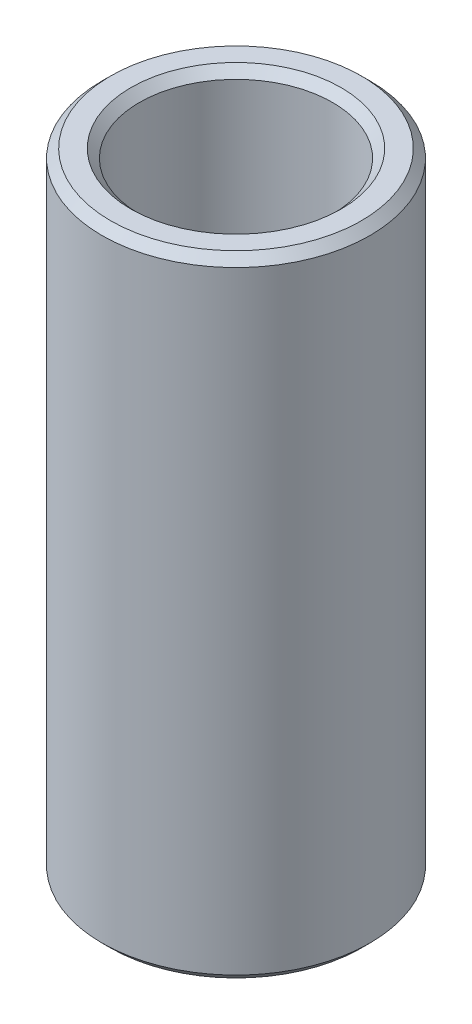
SolidWorks part; units mm, degrees
ref_plane "Front Plane" through (0, 0, 0) normal (0, 0, 1) x (1, 0, 0)
ref_plane "Top Plane" through (0, 0, 0) normal (0, 1, 0) x (1, 0, 0)
ref_plane "Right Plane" through (0, 0, 0) normal (1, 0, 0) x (0, 0, -1)
sketch "Sketch1" plane through (0, 0, 0) normal (0, 1, 0) x (1, 0, 0)
  circle A0 centre (0, 0) radius 47.5
  dimension "SLEEVE_OD" = 95
extrude "Boss-Extrude1" add sketch "Sketch1" along normal blind 223.3104
sketch "Sketch2" plane through (0, 0, 0) normal (0, 1, 0) x (1, 0, 0)
  circle A0 centre (0, 0) radius 34.2598
  dimension "BORE_D" = 68.5196
extrude "Cut-Extrude1" cut sketch "Sketch2" along normal through all
chamfer "Chamfer1" distance 3.0349 angle 45 4 edges at (0, 223.3104, 34.2598) (0, 0, 34.2598) (0, 0, 47.5) (0, 223.3104, 47.5)
